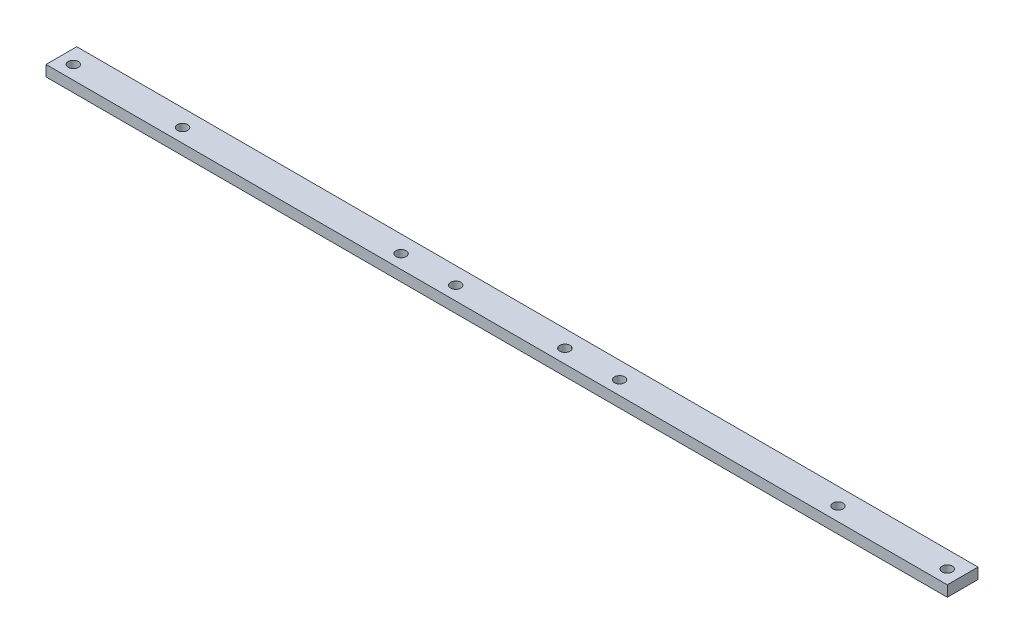
SolidWorks part; units mm, degrees
ref_plane "Front" through (0, 0, 0) normal (0, 0, 1) x (1, 0, 0)
ref_plane "Top" through (0, 0, 0) normal (0, 1, 0) x (1, 0, 0)
ref_plane "Right" through (0, 0, 0) normal (1, 0, 0) x (0, 0, -1)
sketch "Sketch1" plane through (0, 0, 0) normal (0, 1, 0) x (1, 0, 0)
  line L0 (0, 25.5356) -> (0, -1.4644)
  line L3 (0, 25.5356) -> (264, 25.5356)
  line L7 (0, -1.4644) -> (264, -1.4644)
  line L8 (264, -1.4644) -> (264, 25.5356)
  line L9 (264, -1.4644) -> (264, 8.5356)
  line L10 (264, 21.5356) -> (260, 21.5356)
  line L11 (0, 21.5356) -> (4, 21.5356)
  line L12 (4, 21.5356) -> (260, 21.5356)
  line L13 (4, 21.5356) -> (132, 21.5356)
  line L14 (132, 21.5356) -> (260, 21.5356)
  line L15 (264, 8.5356) -> (264, -1.4644)
  line L16 (264, 3.5356) -> (260, 3.5356)
  line L17 (132, 25.5356) -> (132, 23.5356)
  line L18 (4, 21.5356) -> (68, 21.5356)
  line L19 (68, 21.5356) -> (36, 21.5356)
  line L20 (36, 21.5356) -> (36, 3.5356)
  line L21 (196, 21.5356) -> (260, 21.5356)
  line L22 (228, 21.5356) -> (228, 3.5356)
  line L23 (132, 21.5356) -> (132, 4.5356)
  line L24 (132, 21.5356) -> (164, 21.5356)
  circle A0 centre (4, 21.5356) radius 2
  circle A1 centre (260, 21.5356) radius 2
  circle A2 centre (132, 21.5356) radius 2
  circle A3 centre (68, 21.5356) radius 2
  circle A4 centre (196, 21.5356) radius 2
  circle A5 centre (260, 3.5356) radius 1.5
  circle A6 centre (4, 3.5356) radius 1.5
  circle A7 centre (36, 3.5356) radius 1.5
  circle A8 centre (228, 3.5356) radius 1.5
  circle A9 centre (132, 4.5356) radius 1.5
  circle A10 centre (164, 21.5356) radius 2
  circle A11 centre (100, 21.5356) radius 2
  dimension "D5" = 23
  dimension "D6" = 128
  dimension "D9" = 4
  dimension "D10" = 32
  dimension "D11" = 4
  dimension "D1" = 4
  dimension "D2" = 264
  dimension "D3" = 4
  dimension "D4" = 4
  dimension "D7" = 128
  dimension "D8" = 10
  dimension "D12" = 0
  dimension "D13" = 0
extrude "Boss-Extrude1" add sketch "Sketch1" along normal blind 3.175 contours A1 L10 L3 A0 | A1 A0 L10 | A3 L13 A2 L17 L3 L0 L11 A0 | A9 | A0 | A1 region at (65.9183, 0, -23.5857) region at (1, 0, -18.8856) region at (198.0817, 0, -23.5857)
sketch "Sketch2" plane through (0, 3.175, 0) normal (0, 1, 0) x (1, 0, 0)
  line L0 (37.5, 3.5356) -> (228, 3.5356)
  line L1 (132, 21.5356) -> (132, 3.5356)
  line L2 (132, 3.5356) -> (148, 3.5356)
  line L3 (148, 3.5356) -> (116, 3.5356)
  line L4 (116, 3.5356) -> (100, 3.5356)
  line L5 (148, 3.5356) -> (164, 3.5356)
  circle A0 centre (36, 3.5356) radius 1.5 construction
  circle A1 centre (116, 3.5356) radius 1.5
  circle A2 centre (148, 3.5356) radius 1.5
  circle A3 centre (100, 3.5356) radius 1.5
  circle A4 centre (164, 3.5356) radius 1.5
  dimension "D3" = 16
  dimension "D1" = 16
  dimension "D2" = 16
  dimension "D4" = 16
extrude "Cut-Extrude1" cut sketch "Sketch2" against normal blind 10 contours A3 | A1 | A2 | A4
sketch "Sketch3" plane through (0, 3.175, 0) normal (0, 1, 0) x (1, 0, 0)
  line L1 (0, 25.5356) -> (264, 25.5356)
  line L6 (264, 10.5356) -> (264, 25.5356)
  line L8 (264, 10.5356) -> (0, 10.5356)
  line L9 (0, 10.5356) -> (0, 25.5356)
  dimension "D1" = 15
extrude "Cut-Extrude2" cut sketch "Sketch3" against normal blind 10
sketch "Sketch4" plane through (0, 3.175, 0) normal (0, 1, 0) x (1, 0, 0)
  line L0 (0, 12.0356) -> (264, 12.0356)
  line L1 (0, 12.0356) -> (0, 8.5356)
  line L2 (264, 12.0356) -> (264, 8.5356)
  line L3 (0, 8.5356) -> (264, 8.5356)
  line L4 (0, 12.0356) -> (264, 12.0356) construction
  dimension "D1" = 3.5
extrude "Cut-Extrude3" cut sketch "Sketch4" against normal blind 11.5
sketch "Sketch5" plane through (0, 3.175, 0) normal (0, 1, 0) x (1, 0, 0)
  line L0 (0, 8.5356) -> (0, -1.4644) construction
  line L1 (264, -1.4644) -> (0, -1.4644)
  line L2 (264, -1.4644) -> (264, -0.4644)
  line L3 (264, -0.4644) -> (0, -0.4644)
  line L4 (0, -1.4644) -> (0, -0.4644)
  dimension "D1" = 1
extrude "Cut-Extrude4" cut sketch "Sketch5" against normal blind 10
